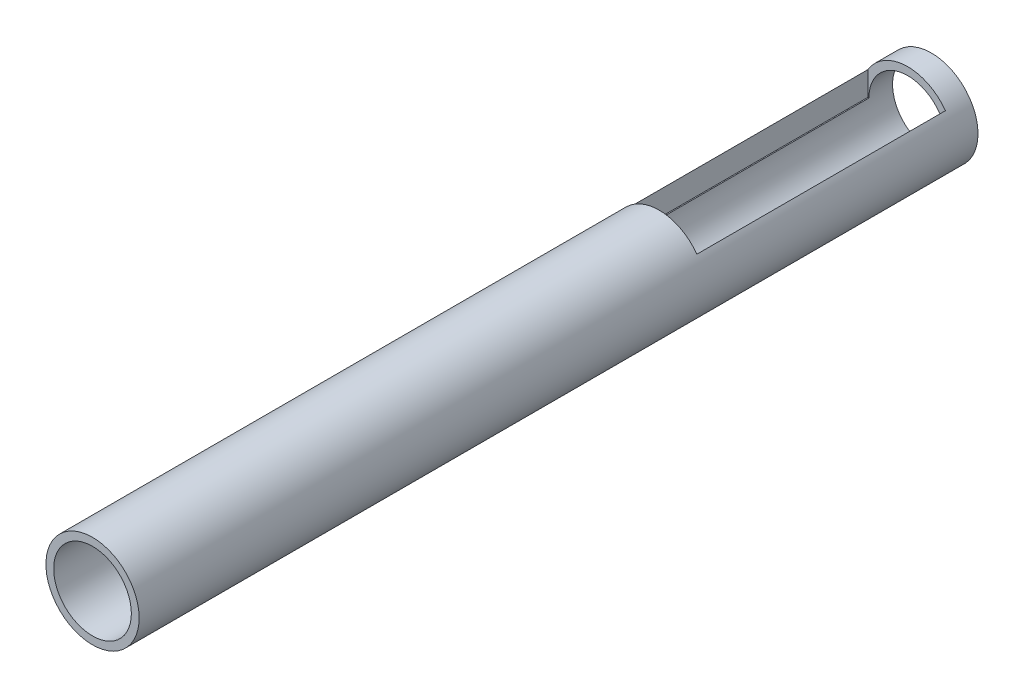
SolidWorks part; units mm, degrees
ref_plane "Front Plane" through (0, 0, 0) normal (0, 0, 1) x (1, 0, 0)
ref_plane "Top Plane" through (0, 0, 0) normal (0, 1, 0) x (1, 0, 0)
ref_plane "Right Plane" through (0, 0, 0) normal (1, 0, 0) x (0, 0, -1)
sketch "Sketch3" plane through (0, 0, 0) normal (0, 0, 1) x (1, 0, 0)
  circle A0 centre (0, 0) radius 38.1
  circle A1 centre (0, 0) radius 31.75
  dimension "D1" = 76.2
  dimension "D2" = 63.5
extrude "Boss-Extrude3" add sketch "Sketch3" along normal blind 685.8
sketch "Sketch4" plane through (0, 0, 0) normal (0, 1, 0) x (1, 0, 0)
  line L1 (-32.6424, -19.3531) -> (30.8576, -19.3531)
  line L2 (-32.6424, -19.3531) -> (-32.6424, -222.5531)
  line L3 (-32.6424, -222.5531) -> (30.8576, -222.5531)
  line L4 (30.8576, -19.3531) -> (30.8576, -222.5531)
  dimension "D1" = 63.5
  dimension "D2" = 203.2
extrude "Cut-Extrude2" cut sketch "Sketch4" along normal blind 685.8
